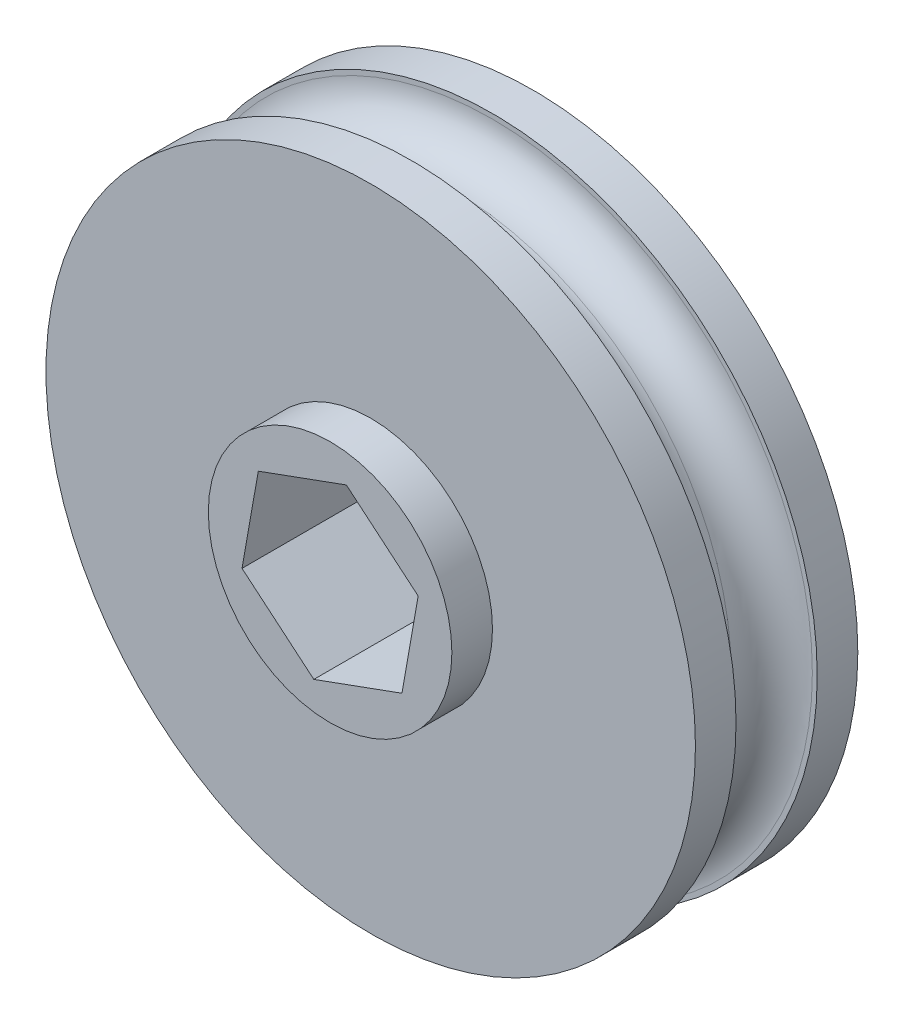
SolidWorks part; units mm, degrees
material "Nylon 101"
ref_plane "Front Plane" through (0, 0, 0) normal (0, 0, 1) x (1, 0, 0)
ref_plane "Top Plane" through (0, 0, 0) normal (0, 1, 0) x (1, 0, 0)
ref_plane "Right Plane" through (0, 0, 0) normal (1, 0, 0) x (0, 0, -1)
sketch "Sketch1" plane through (0, 0, 0) normal (0, 0, 1) x (1, 0, 0)
  circle A1 centre (0, 0) radius 25.4
  dimension "D2" = 50.8
extrude "Boss-Extrude1" add sketch "Sketch1" along normal blind 12.7
ref_plane "Plane1" through (0, 0, 9.525) normal (0, 0, 1) x (1, 0, 0)
sketch "Sketch2" plane through (0, 0, 9.525) normal (0, 0, 1) x (1, 0, 0)
  circle A0 centre (0, 0) radius 21.844
  circle A1 centre (0, 0) radius 25.4
  dimension "D1" = 43.688
  dimension "D2" = 50.8
extrude "Cut-Extrude1" cut sketch "Sketch2" against normal blind 6.35
fillet "Fillet1" radius 3.175 2 edges at (21.844, 0, 9.525) (21.844, 0, 3.175)
sketch "Sketch3" plane through (0, 0, 12.7) normal (0, 0, 1) x (1, 0, 0)
  line L1 (-1.2727, -7.2211) -> (5.6173, -4.7127)
  line L2 (5.6173, -4.7127) -> (6.89, 2.5084)
  line L3 (6.89, 2.5084) -> (1.2727, 7.2211)
  line L4 (1.2727, 7.2211) -> (-5.6173, 4.7127)
  line L5 (-5.6173, 4.7127) -> (-6.89, -2.5084)
  line L6 (-6.89, -2.5084) -> (-1.2727, -7.2211)
  circle A0 centre (0, 0) radius 6.35 construction
  dimension "D1" = 12.7
extrude "Cut-Extrude4" cut sketch "Sketch3" against normal up to surface (12.7 mm away) up to face at (25.4, 0, 0)
sketch "Sketch6" plane through (0, 0, 12.7) normal (0, 0, 1) x (1, 0, 0)
  line L1 (-1.2727, -7.2211) -> (5.6173, -4.7127)
  line L2 (5.6173, -4.7127) -> (6.89, 2.5084)
  line L3 (6.89, 2.5084) -> (1.2727, 7.2211)
  line L4 (1.2727, 7.2211) -> (-5.6173, 4.7127)
  line L5 (-5.6173, 4.7127) -> (-6.89, -2.5084)
  line L6 (-6.89, -2.5084) -> (-1.2727, -7.2211)
  circle A0 centre (0, 0) radius 9.525
  circle A1 centre (0, 0) radius 6.35 construction
  dimension "D1" = 19.05
  dimension "D2" = 12.7
extrude "Boss-Extrude4" add sketch "Sketch6" along normal blind 3.175
